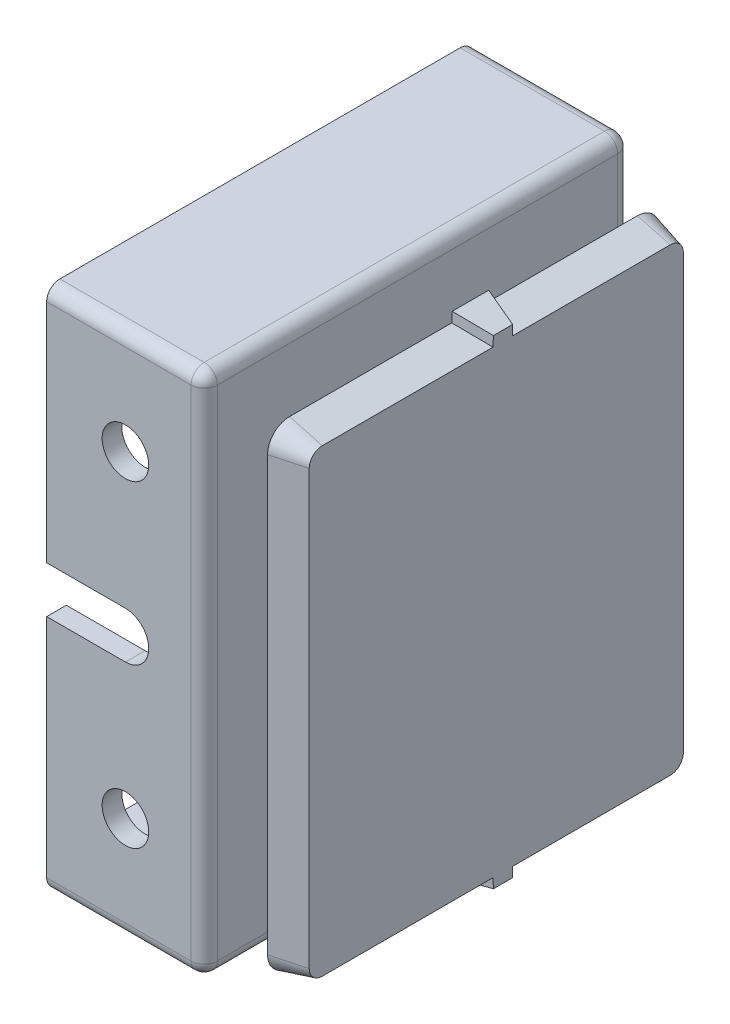
SolidWorks part; units mm, degrees
other "COVER"
ref_plane "Front Plane" through (0, 0, 0) normal (1, 0, 0) x (0, 1, 0)
ref_plane "Top Plane" through (0, 0, 0) normal (0, 0, 1) x (0, 1, 0)
ref_plane "Right Plane" through (0, 0, 0) normal (0, 1, 0) x (-1, 0, 0)
sketch "Sketch1" plane through (0, 0, 0) normal (0, 0, 1) x (0, 1, 0)
  line L1 (-40, -12) -> (40, -12)
  line L2 (-40, -12) -> (-40, 12)
  line L3 (-40, 12) -> (40, 12)
  line L4 (40, -12) -> (40, 12)
  line L5 (-40, -12) -> (40, 12) construction
  line L6 (-40, 12) -> (40, -12) construction
  line L7 (0, 12) -> (0, -12) construction
  circle A0 centre (0, 0) radius 3
  point P0 (0, 0)
  dimension "D3" = 6
  dimension "D1" = 24
  dimension "D2" = 80
extrude "Boss-Extrude1" add sketch "Sketch1" along normal blind 65 contours L1 L4 L3 L2 A0 | A0 region at (0, -39.1648, 0) region at (0, 0, 0)
shell "2 mm top/bot 3 mm side" thickness 3 removed face at (-12, 0, 32.5)
sketch "Sketch3" plane through (0, 0, 0) normal (0, 0, -1) x (1, 0, 0)
  line L0 (0, 40) -> (0, -40) construction
  line L1 (12, 40) -> (-12, 40) construction
  line L2 (12, -40) -> (-12, -40) construction
  line L3 (0, 40) -> (0, 27.4)
  line L4 (0, -40) -> (0, -27.4)
  circle A0 centre (0, 22.5) radius 4.9
  circle A1 centre (0, 7.5) radius 4.9
  circle A2 centre (0, -7.5) radius 4.9
  circle A3 centre (0, -22.5) radius 4.9
  dimension "D1" = 9.8
  dimension "D2" = 4
extrude "9.8 mm port holes" cut sketch "Sketch3" against normal up to surface (3 mm away) contours L0 A0 | A0 L0 | A1 L0 | L0 A1 | A2 L0 | L0 A2 | L0 A3 | A3 L0 region at (2.0796, -22.5, 0) region at (2.0796, 22.5, 0) region at (-2.0796, 22.5, 0) region at (2.0796, 7.5, 0) region at (-2.0796, 7.5, 0) region at (2.0796, -7.5, 0) region at (-2.0796, -7.5, 0) region at (-2.0796, -22.5, 0) up to face at (-1.5, 0, 3)
sketch "Sketch4" plane through (0, 0, 65) normal (0, 0, 1) x (1, 0, 0)
  line L0 (0, 40) -> (0, -40) construction
  line L1 (12, 40) -> (-12, 40) construction
  line L2 (12, -40) -> (-12, -40) construction
  line L3 (0, 3.55) -> (0, 20.65)
  line L4 (-12, 0) -> (12, 0) construction
  line L5 (-12, -40) -> (-12, 40) construction
  line L6 (12, -40) -> (12, 40) construction
  line L7 (0, 3.55) -> (-12, 3.55)
  line L8 (0, -3.55) -> (-12, -3.55)
  line L9 (-12, -3.55) -> (-12, 3.55)
  circle A0 centre (0, 0) radius 3.55
  circle A1 centre (0, 24.2) radius 3.55
  circle A2 centre (0, -24.2) radius 3.55
  line M6 (-12, 40) -> (-12, -40)
  dimension "D1" = 7.1
  dimension "D2" = 17.1
extrude "7.1 mm fixture holes" cut sketch "Sketch4" along direction (0, 0, 1) on the side against the normal blind 10 contours A1 | A0 | A2 | A0 L7 L8 M6 region at (0, 24.2, 65) region at (-7.36, 0, 65) region at (0, 0, 65) region at (0, -24.2, 65)
fillet "2 mm radius" radius 2 4 edges at (9, 35, 32.5) (9, -35, 32.5) (12, -40, 32.5) (12, 40, 32.5)
sketch "Sketch7" plane through (0, 40, 0) normal (0, 1, 0) x (-1, 0, 0)
  line L0 (1, 65) -> (1, 0) construction
  line L1 (-10, 65) -> (12, 65) construction
  line L2 (-10, 0) -> (12, 0) construction
  circle A0 centre (1, 32.5) radius 4.25
  dimension "D1" = 8.5
extrude "8.5 mm hold offset 2 mm" cut sketch "Sketch7" against normal blind 3.2 from offset 2 offset against normal yes
mirror "magnet slot mirror" about plane through (0, 0, 0) normal (0, 1, 0) of "8.5 mm hold offset 2 mm"
fillet "R2 filet" radius 2 20 edges at (8.4142, -34.4142, 62) (9, 0, 62) (8.4142, 34.4142, 62) (8.4142, -34.4142, 3) (9, 0, 3) (8.4142, 34.4142, 3) (-2.5, -35, 62) (-2.5, 35, 62) (-2.5, -35, 3) (-2.5, 35, 3) (-1, -40, 65) (11.4142, -39.4142, 65) (12, 0, 65) (11.4142, 39.4142, 65) (-1, 40, 0) (11.4142, 39.4142, 0) (12, 0, 0) (11.4142, -39.4142, 0) (-1, 40, 65) (-1, -40, 0)
sketch "Sketch8" plane through (-12, 0, 0) normal (-1, 0, 0) x (0, -1, 0)
  line L0 (-35, 5) -> (-35, 60) construction
  line L1 (-36.5, 31) -> (-33.5, 31)
  line L2 (-36.5, 31) -> (-36.5, 34)
  line L3 (-36.5, 34) -> (-33.5, 34)
  line L4 (-33.5, 31) -> (-33.5, 34)
  line L5 (-36.5, 31) -> (-33.5, 34) construction
  line L6 (-36.5, 34) -> (-33.5, 31) construction
  point P0 (-35, 32.5)
  dimension "D1" = 3
extrude "7 mm notch" cut sketch "Sketch8" against normal blind 7
mirror "7 mm notch mirror" about plane through (0, 0, 0) normal (0, 1, 0) of "7 mm notch"
sketch "Sketch9" plane through (0, 0, 0) normal (1, 0, 0) x (0, 1, 0)
  line L0 (0, 0) -> (0, 65) construction
  line L1 (-38, 65) -> (38, 65) construction
  line L2 (35, 62) -> (35, 34) construction
  line L8 (33, 5) -> (-33, 5) construction
  line L9 (33, 62) -> (-33, 62)
  line L10 (35, 60) -> (35, 34)
  line L11 (33, 5) -> (-33, 5)
  line L12 (0, 62) -> (0, 5)
  line L13 (35, 62) -> (0, 5) construction
  line L14 (35, 5) -> (0, 62) construction
  line L15 (35, 31) -> (36.5, 31)
  line L16 (36.5, 31) -> (36.5, 33.9361)
  line L17 (36.5, 33.9361) -> (35, 34)
  line L18 (35, 31) -> (35, 3) construction
  line L19 (35, 31) -> (35, 7)
  line L20 (-35, 31) -> (-35, 3) construction
  line L21 (-35, 5) -> (0, 62) construction
  line L22 (-35, 62) -> (0, 5) construction
  line L23 (-35, 62) -> (-35, 34) construction
  line L24 (-35, 31) -> (-35, 7)
  line L25 (-36.5, 33.9361) -> (-35, 34)
  line L26 (-36.5, 31) -> (-36.5, 33.9361)
  line L27 (-35, 31) -> (-36.5, 31)
  line L28 (-35, 60) -> (-35, 34)
  arc A0 (35, 7) -> (33, 5) centre (33, 7) cw
  arc A1 (35, 60) -> (33, 62) centre (33, 60) ccw
  arc A2 (-35, 60) -> (-33, 62) centre (-33, 60) cw
  arc A3 (-35, 7) -> (-33, 5) centre (-33, 7) ccw
  point P10 (17.5, 33.5)
  point P42 (-17.5, 33.5)
  dimension "D1" = 2
extrude "Boss-Extrude2" add sketch "Sketch9" against normal blind 5 from offset 25 contours L10 A1 L9 L12 L11 A0 L19 L15 L16 L17 | L24 A3 L11 L12 L9 A2 L28 L25 L26 L27 region at (0, 17.526, 33.4977) region at (0, -17.526, 33.4977)
draft "Draft2" type of draft neutral plane draft angle 15 faces to draft 14 face at (22.5, -35, 47) face at (22.5, -36.5, 32.4681) face at (22.5, -35, 19) face at (22.5, -34.2071, 5.7929) face at (22.5, 0, 5) face at (22.5, 34.2071, 5.7929) face at (22.5, 35, 19) face at (22.5, 35.75, 31) face at (22.5, 36.5, 32.4681) face at (22.5, 35.75, 33.9681) face at (22.5, 35, 47) face at (22.5, 34.2071, 61.2071) face at (22.5, 0, 62) face at (22.5, -34.2071, 61.2071) neutral plane through (25, 0, 0) neutral plane normal (1, 0, 0) parameters "D1"=15
